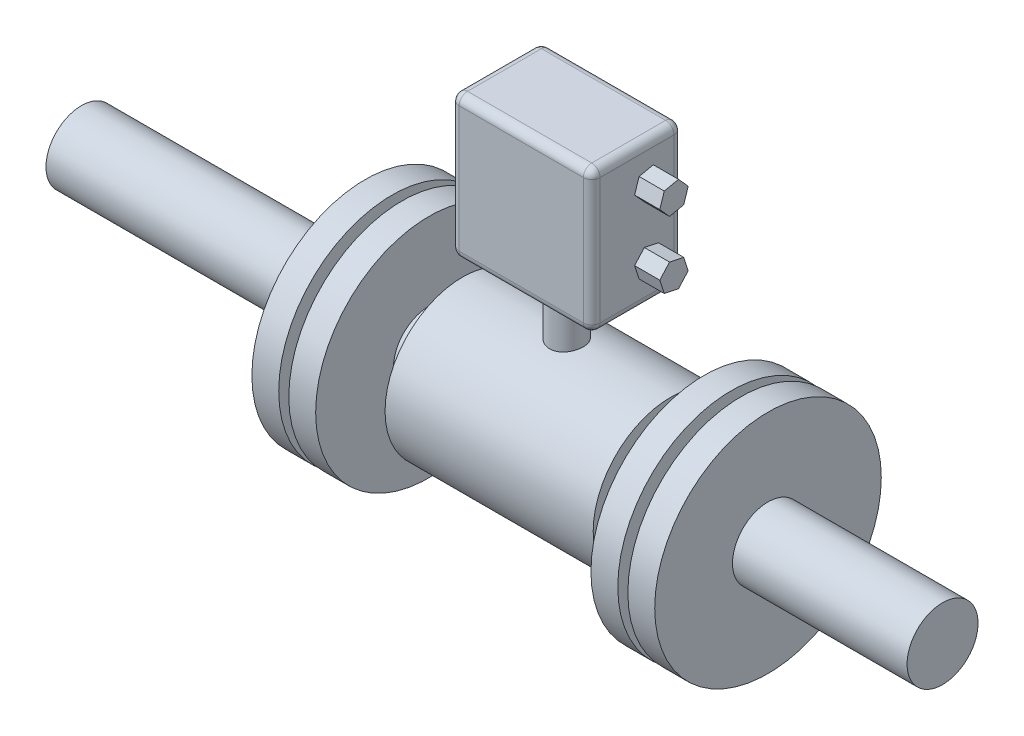
SolidWorks part; units mm, degrees
ref_plane "Спереди" through (0, 0, 0) normal (0, 0, 1) x (1, 0, 0)
ref_plane "Сверху" through (0, 0, 0) normal (0, 1, 0) x (1, 0, 0)
ref_plane "Справа" through (0, 0, 0) normal (1, 0, 0) x (0, 0, -1)
sketch "Эскиз3" plane through (0, 0, 0) normal (0, 1, 0) x (1, 0, 0)
  line L0 (-117.2936, 0) -> (140.6915, 0) construction
  line L1 (0, 70.9473) -> (0, -61.1615) construction
  line L2 (101, 75.5557) -> (101, -103.1048) construction
  line L3 (82, -67.5) -> (98, -67.5)
  line L4 (98, -67.5) -> (98, -33)
  line L5 (98, -33) -> (104, -33)
  line L6 (82, -67.5) -> (82, -21.15)
  line L7 (82, -21.15) -> (62, -21.15)
  line L8 (62, -21.15) -> (62, -46.15)
  line L9 (62, -46.15) -> (-62, -46.15)
  line L10 (-62, -21.15) -> (-62, -46.15)
  line L11 (-82, -21.15) -> (-62, -21.15)
  line L12 (-82, -67.5) -> (-82, -21.15)
  line L13 (-98, -33) -> (-104, -33)
  line L14 (-98, -67.5) -> (-98, -33)
  line L15 (-82, -67.5) -> (-98, -67.5)
  line L16 (-101, 82.6468) -> (-101, -100.7312) construction
  line L17 (224, 0) -> (-289, 0)
  line L18 (120, -67.5) -> (104, -67.5)
  line L19 (104, -67.5) -> (104, -33)
  line L20 (120, -67.5) -> (120, -21.15)
  line L21 (-120, -67.5) -> (-104, -67.5)
  line L22 (-104, -67.5) -> (-104, -33)
  line L23 (-120, -67.5) -> (-120, -21.15)
  line L24 (-120, -21.15) -> (-289, -21.15)
  line L25 (-289, -21.15) -> (-289, 0)
  line L26 (120, -21.15) -> (224, -21.15)
  line L27 (224, -21.15) -> (224, 0)
  point P13 (0, -46.15)
  point P29 (101, -33)
  point P32 (-101, -33)
  dimension "D1" = 3
  dimension "S" = 16
  dimension "D5" = 20
  dimension "D6" = 25
  dimension "L" = 202
  dimension "Дн трубы" = 21.15
  dimension "Д1" = 67.5
  dimension "Д" = 33
  dimension "L2" = 185
  dimension "L1" = 120
revolve "Повернуть2" add sketch "Эскиз3" angle 360 about L0
sketch "Эскиз4" plane through (0, 0, 0) normal (0, 1, 0) x (1, 0, 0)
  circle A0 centre (0, 0) radius 10
  dimension "D1" = 20
extrude "Вытянуть3" add sketch "Эскиз4" along normal blind 165.5
sketch "Эскиз5" plane through (0, 165.5, 0) normal (0, 1, 0) x (-1, 0, 0)
  line L1 (42, -27) -> (-42, -27)
  line L2 (42, -27) -> (42, 27)
  line L3 (42, 27) -> (-42, 27)
  line L4 (-42, -27) -> (-42, 27)
  line L5 (42, -27) -> (-42, 27) construction
  line L6 (42, 27) -> (-42, -27) construction
  point P0 (0, 0)
  dimension "D1" = 84
  dimension "D2" = 54
extrude "Вытянуть4" add sketch "Эскиз5" against normal blind 85
fillet "Скругление1" radius 5 12 edges at (42, 165.5, 0) (0, 165.5, 27) (0, 165.5, -27) (-42, 165.5, 0) (-42, 123, -27) (-42, 80.5, 0) (0, 80.5, -27) (42, 80.5, 0) (0, 80.5, 27) (-42, 123, 27) (42, 123, -27) (42, 123, 27)
sketch "Эскиз6" plane through (42, 0, 0) normal (1, 0, 0) x (0, 0, -1)
  line L0 (7, 160.5) -> (7, 85.5) construction
  line L1 (-22, 160.5) -> (-22, 85.5) construction
  line L2 (27, 160.5) -> (27, 85.5) construction
  line L3 (-22, 123) -> (7, 123) construction
  line L4 (4.3214, 134.7644) -> (12.7929, 136.5624)
  line L5 (12.7929, 136.5624) -> (15.4715, 144.798)
  line L6 (15.4715, 144.798) -> (9.6786, 151.2356)
  line L7 (9.6786, 151.2356) -> (1.2071, 149.4376)
  line L8 (1.2071, 149.4376) -> (-1.4715, 141.202)
  line L9 (-1.4715, 141.202) -> (4.3214, 134.7644)
  line L10 (-22, 85.5) -> (22, 85.5) construction
  line L11 (22, 160.5) -> (-22, 160.5) construction
  line L12 (-1.4715, 104.798) -> (4.3214, 111.2356)
  line L13 (1.2071, 96.5624) -> (-1.4715, 104.798)
  line L14 (9.6786, 94.7644) -> (1.2071, 96.5624)
  line L15 (15.4715, 101.202) -> (9.6786, 94.7644)
  line L16 (12.7929, 109.4376) -> (15.4715, 101.202)
  line L17 (4.3214, 111.2356) -> (12.7929, 109.4376)
  circle A0 centre (7, 143) radius 7.5 construction
  circle A1 centre (7, 103) radius 7.5 construction
  dimension "D2" = 15
  dimension "D1" = 20
  dimension "D3" = 20
extrude "Вытянуть5" add sketch "Эскиз6" along normal blind 15
ref_axis "Ось1" through (-120, 0, 0) along (-1, 0, 0)
